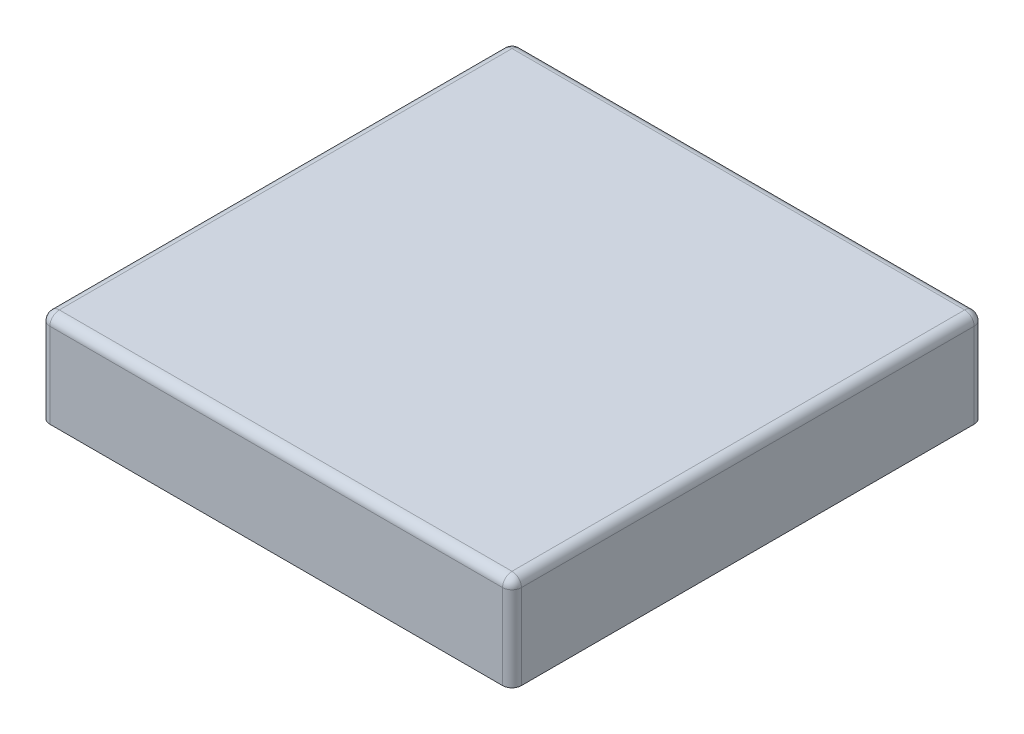
SolidWorks part; units mm, degrees
ref_plane "Front Plane" through (0, 0, 0) normal (0, 0, 1) x (1, 0, 0)
ref_plane "Top Plane" through (0, 0, 0) normal (0, 1, 0) x (1, 0, 0)
ref_plane "Right Plane" through (0, 0, 0) normal (1, 0, 0) x (0, 0, -1)
sketch "Sketch1" plane through (0, 0, 0) normal (0, 1, 0) x (1, 0, 0)
  line L1 (0, 0) -> (5, 0)
  line L2 (0, 0) -> (0, 5)
  line L3 (0, 5) -> (5, 5)
  line L4 (5, 0) -> (5, 5)
  dimension "D1" = 5
extrude "Boss-Extrude1" add sketch "Sketch1" along normal blind 1
fillet "Fillet1" radius 0.1 4 edges at (0, 1, -2.5) (2.5, 1, 0) (5, 1, -2.5) (2.5, 1, -5)
fillet "Fillet2" radius 0.1 8 edges at (4.9707, 0.9707, -0.0293) (4.9707, 0.9707, -4.9707) (0.0293, 0.9707, -4.9707) (0.0293, 0.9707, -0.0293) (5, 0.45, 0) (5, 0.45, -5) (0, 0.45, -5) (0, 0.45, 0)
